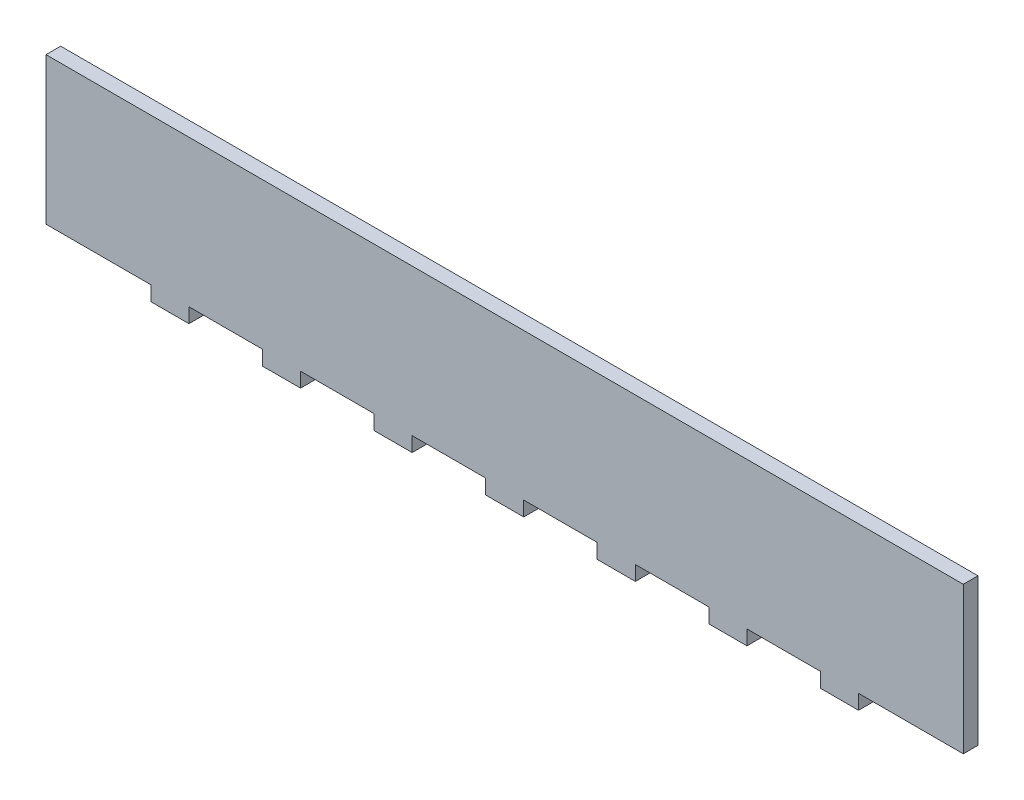
SolidWorks part; units mm, degrees
material "Oak"
ref_plane "Front Plane" through (0, 0, 0) normal (0, 0, 1) x (1, 0, 0)
ref_plane "Top Plane" through (0, 0, 0) normal (0, 1, 0) x (1, 0, 0)
ref_plane "Right Plane" through (0, 0, 0) normal (1, 0, 0) x (0, 0, -1)
sketch "Sketch1" plane through (0, 0, 0) normal (0, 0, 1) x (1, 0, 0)
  line L1 (-93.7, 15) -> (93.7, 15)
  line L2 (-93.7, 15) -> (-93.7, -15)
  line L3 (-93.7, -15) -> (93.7, -15)
  line L4 (93.7, 15) -> (93.7, -15)
  point P7 (-44.0158, 2.5238)
  point P8 (-44.0158, 0.4482)
  dimension "D1" = 30
  dimension "D2" = 187.4
  dimension "D3" = 15
  dimension "D4" = 93.7
extrude "Boss-Extrude1" add sketch "Sketch1" along normal blind 3
sketch "Sketch2" plane through (0, -15, 0) normal (0, -1, 0) x (1, 0, 0)
  line L0 (-93.7, 3) -> (93.7, 3) construction
  line L1 (-3.9, 3) -> (3.9, 3)
  line L2 (-3.9, 3) -> (-3.9, 0)
  line L3 (-3.9, 0) -> (3.9, 0)
  line L4 (3.9, 3) -> (3.9, 0)
  line L5 (55, 0) -> (-55, 0) construction
  line L6 (0, -55) -> (0, 55) construction
  dimension "D1" = 7.8
  dimension "D2" = 3.9
extrude "Boss-Extrude2" add sketch "Sketch2" along normal blind 3
pattern_linear "LPattern2" count 4 spacing 22.8 along (1, 0, 0) count 4 spacing 22.8 along (-1, 0, 0) of "Boss-Extrude2"
